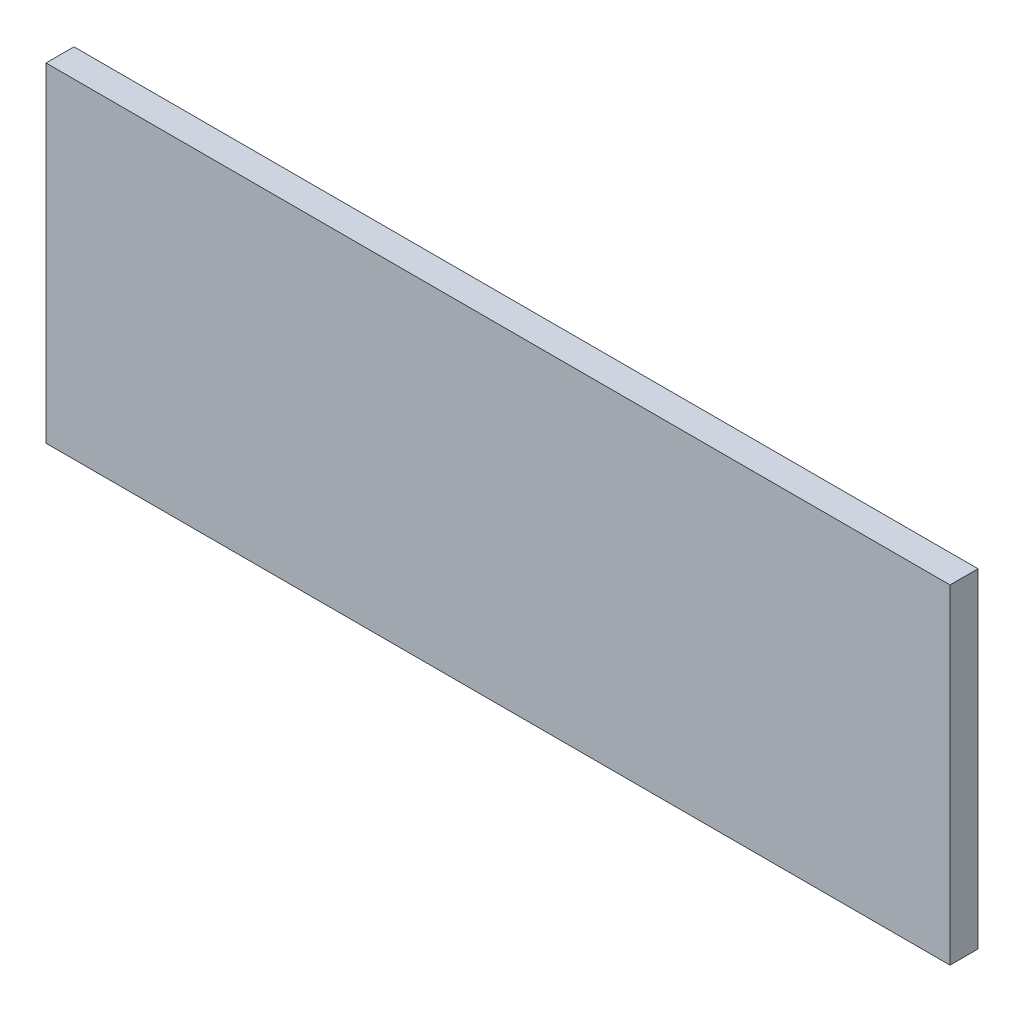
SolidWorks part; units mm, degrees
ref_plane "正面" through (0, 0, 0) normal (0, 0, 1) x (1, 0, 0)
ref_plane "平面" through (0, 0, 0) normal (0, 1, 0) x (1, 0, 0)
ref_plane "右側面" through (0, 0, 0) normal (1, 0, 0) x (0, 0, -1)
sketch "ｽｹｯﾁ1" plane through (0, 0, 0) normal (0, 0, 1) x (1, 0, 0)
  line L1 (-69.2801, 161.5071) -> (350.7199, 161.5071)
  line L2 (-69.2801, 161.5071) -> (-69.2801, 8.5071)
  line L3 (-69.2801, 8.5071) -> (350.7199, 8.5071)
  line L4 (350.7199, 161.5071) -> (350.7199, 8.5071)
  dimension "D1" = 420
  dimension "D3" = 153
extrude "ﾎﾞｽ - 押し出し1" add sketch "ｽｹｯﾁ1" along normal blind 13
